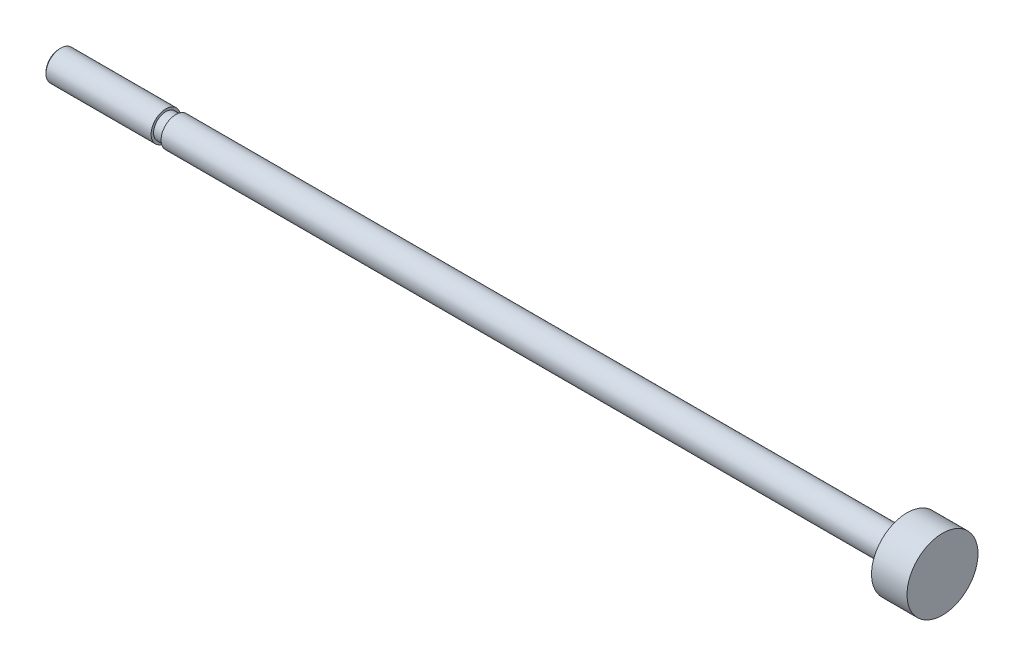
SolidWorks part; units mm, degrees
ref_plane "Front Plane" through (0, 0, 0) normal (0, 0, 1) x (1, 0, 0)
ref_plane "Top Plane" through (0, 0, 0) normal (0, 1, 0) x (1, 0, 0)
ref_plane "Right Plane" through (0, 0, 0) normal (1, 0, 0) x (0, 0, -1)
sketch "Sketch1" plane through (0, 0, 0) normal (1, 0, 0) x (0, 0, -1)
  circle A0 centre (0, 0) radius 5
  circle A1 centre (0, 0) radius 2.1827
  circle A2 centre (0, 0) radius 1.9328
  circle A3 centre (0, 0) radius 1.7328
  circle A4 centre (0, 0) radius 2.0828
extrude "Boss-Extrude2" add sketch "Sketch1" against normal blind 5 contours A3 | A2 A3 | A4 A2 | A1 A4 | A0 A1 region at (0, 0, 4.8586) region at (0, 0, 2.121) region at (0, 0, 1.8781) region at (0, 0, 0) region at (0, 0, 2.0239)
extrude "Boss-Extrude3" add sketch "Sketch1<5>" against normal blind 107.9999 contours A4
sketch "Sketch1<5>" plane through (0, 0, 0) normal (1, 0, 0) x (0, 0, -1) same geometry as "Sketch1"
extrude "Boss-Extrude4" add sketch "Sketch1<6>" against normal blind 0.1999 from surface contours A2 starting at face at (-107.9999, 0, -2.0828)
sketch "Sketch1<6>" plane through (0, 0, 0) normal (1, 0, 0) x (0, 0, -1) same geometry as "Sketch1"
extrude "Boss-Extrude5" add sketch "Sketch1<7>" against normal blind 1.1999 from surface contours A3 starting at face at (-108.1998, 0, -1.9328)
sketch "Sketch1<7>" plane through (0, 0, 0) normal (1, 0, 0) x (0, 0, -1) same geometry as "Sketch1"
extrude "Boss-Extrude6" add sketch "Sketch1<8>" against normal blind 15 from surface contours A4 starting at face at (-109.3997, 0, -1.7328)
sketch "Sketch1<8>" plane through (0, 0, 0) normal (1, 0, 0) x (0, 0, -1) same geometry as "Sketch1"
chamfer "Chamfer1" distance 0.2032 angle 45 1 edges at (-108.1998, 0, -1.9328)
chamfer "Chamfer2" distance 0.1905 angle 45 1 edges at (-124.3996, 0, -2.0828)
equation "\"D2@Sketch1\"=.164 + .00787"
equation "\"D1@Boss-Extrude3\"=1.66in + .7874 - 0.16394 + 50mm"
equation "\"D3@Sketch1\"=0.17187in - 0.01968"
equation "\"D4@Sketch1\"=\"D3@Sketch1\" - .01575"
